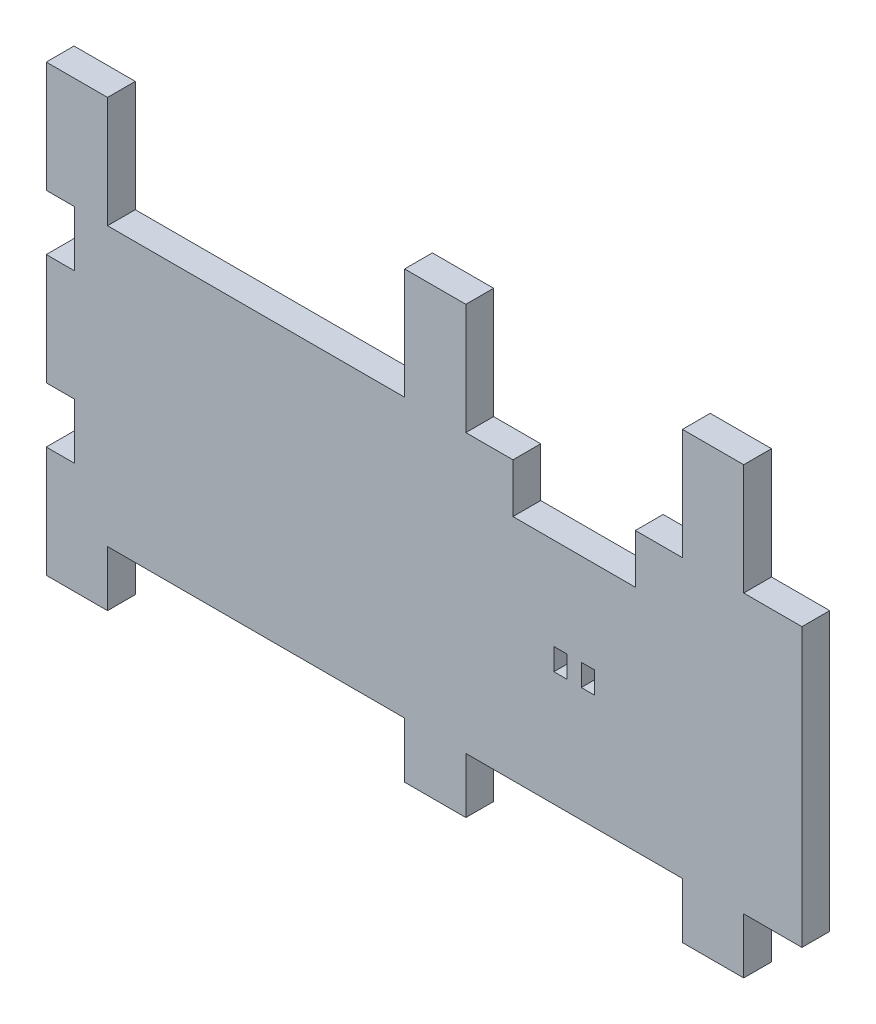
SolidWorks part; units mm, degrees
ref_plane "Front Plane" through (0, 0, 0) normal (0, 0, 1) x (1, 0, 0)
ref_plane "Top Plane" through (0, 0, 0) normal (0, 1, 0) x (1, 0, 0)
ref_plane "Right Plane" through (0, 0, 0) normal (1, 0, 0) x (0, 0, -1)
sketch "Sketch2" plane through (0, 0, 0) normal (0, 0, 1) x (1, 0, 0)
  line L1 (-88.9, -50.8) -> (88.9, -50.8)
  line L2 (-88.9, -50.8) -> (-88.9, 50.8)
  line L3 (-88.9, 50.8) -> (88.9, 50.8)
  line L4 (88.9, -50.8) -> (88.9, 50.8)
  line L5 (-88.9, -50.8) -> (88.9, 50.8) construction
  line L6 (-88.9, 50.8) -> (88.9, -50.8) construction
  point P0 (0, 0)
  dimension "D1" = 101.6
  dimension "D2" = 177.8
extrude "Boss-Extrude3" add sketch "Sketch2" along normal blind 6.35
sketch "Sketch3" plane through (0, 0, 6.35) normal (0, 0, 1) x (1, 0, 0)
  line L0 (-88.9, 50.8) -> (-82.55, 50.8)
  line L1 (-88.9, 50.8) -> (-88.9, 35.56)
  line L2 (-88.9, -50.8) -> (88.9, -50.8) construction
  line L3 (-88.9, 50.8) -> (-74.9, 50.8)
  line L4 (88.9, 50.8) -> (-88.9, 50.8) construction
  line L5 (-82.55, 50.8) -> (-76.2, 50.8)
  line L6 (-14.65, 50.8) -> (-0.65, 50.8)
  line L7 (-88.9, 50.8) -> (-88.9, 35.56)
  line L8 (-7, 50.8) -> (5.3812, 50.8)
  line L9 (-82.4404, 0) -> (-82.4404, 12.7)
  line L10 (-88.9, 50.8) -> (-88.9, -50.8) construction
  line L11 (-7, 50.8) -> (-7, 25.4002)
  line L12 (-88.9, 50.8) -> (-88.9, 25.4002) construction
  line L13 (-82.4404, 25.4002) -> (-82.4404, 12.7)
  line L14 (-82.4404, 25.4002) -> (-74.9, 25.4002)
  line L15 (56.509, 25.4002) -> (56.509, 50.8)
  line L16 (56.509, 25.4002) -> (70.509, 25.4002)
  line L17 (56.509, 50.8) -> (70.509, 50.8)
  line L18 (70.509, 25.4002) -> (70.509, 50.8)
  line L19 (70.509, 25.4002) -> (88.9, 25.4002) construction
  line L20 (-82.55, 50.8) -> (-14.65, 50.8) construction
  line L21 (-0.65, 50.8) -> (56.509, 50.8) construction
  line L22 (70.509, 50.8) -> (88.9, 50.8) construction
  line L23 (70.509, -50.8) -> (88.9, -50.8) construction
  line L24 (-74.9, 50.8) -> (-74.9, 25.4002)
  line L25 (-88.9, -38.1) -> (-74.9, -38.1)
  line L26 (-82.55, 50.8) -> (-14.65, 50.8)
  line L27 (-88.9, -38.1) -> (-88.9, -50.8)
  line L28 (-88.9, -50.8) -> (-74.9, -50.8)
  line L29 (-74.9, -38.1) -> (-74.9, -50.8)
  line L30 (-7, -50.8) -> (-7, -38.1)
  line L31 (70.509, 50.8) -> (70.509, 25.4002)
  line L32 (70.509, 25.4002) -> (88.9, 25.4002)
  line L33 (70.509, 25.4002) -> (70.509, 50.8)
  line L34 (70.509, 50.8) -> (88.9, 50.8)
  line L35 (88.9, 25.4002) -> (88.9, 50.8)
  line L36 (7, -50.8) -> (7, -38.1)
  line L37 (0, -50.8) -> (-0.65, 50.8) construction
  line L38 (70.509, -38.1) -> (88.9, -38.1) construction
  line L39 (-7, -38.1) -> (7, -38.1)
  line L40 (-7, -50.8) -> (-7, -38.1)
  line L41 (88.9, -38.1) -> (88.9, -50.8)
  line L42 (70.509, -50.8) -> (88.9, -50.8)
  line L43 (70.509, -38.1) -> (70.509, -50.8)
  line L44 (70.509, -38.1) -> (88.9, -38.1)
  line L45 (70.509, -50.8) -> (70.509, -38.1)
  line L46 (-7, -50.8) -> (7, -50.8)
  line L47 (-88.9, -44.45) -> (-88.9, -25.4) construction
  line L48 (-7, 50.8) -> (7, 50.8)
  line L49 (-7, 50.8) -> (-7, 25.4002)
  line L50 (-7, 25.4002) -> (7, 25.4002)
  line L51 (7, 50.8) -> (7, 25.4002)
  line L52 (-7, -38.1) -> (7, -38.1)
  line L53 (70.509, -38.1) -> (70.509, -50.8)
  line L54 (56.509, -50.8) -> (70.509, -50.8)
  line L55 (56.509, -38.1) -> (70.509, -38.1)
  line L56 (56.509, -38.1) -> (56.509, -50.8)
  line L57 (-7, -38.1) -> (-7, -50.8)
  line L58 (-82.4404, 0) -> (-82.4404, -12.7)
  line L59 (7, -38.1) -> (7, -50.8)
  line L60 (-74.9, -38.1) -> (-7, -38.1)
  line L61 (-74.9, -38.1) -> (-74.9, -50.8)
  line L62 (-74.9, -50.8) -> (-7, -50.8)
  line L63 (-88.9, -50.8) -> (-88.9, -38.1)
  line L64 (-88.9, -50.8) -> (-82.55, -50.8)
  line L65 (-7, -38.1) -> (-7, -50.8)
  line L66 (7, -38.1) -> (56.509, -38.1)
  line L67 (-82.4404, 25.4002) -> (-82.55, 50.8)
  line L68 (7, -38.1) -> (7, -50.8)
  line L69 (-88.9, 35.56) -> (-88.9, -38.1)
  line L70 (7, -50.8) -> (56.509, -50.8)
  line L71 (-88.9, 0) -> (88.9, 0) construction
  line L72 (-88.9, 38.1) -> (-88.9, 25.4002)
  line L76 (-88.9, 25.4002) -> (-82.4404, 25.4002)
  line L78 (56.509, -38.1) -> (56.509, -50.8)
  line L80 (-88.9, 35.56) -> (-88.9, 25.4002)
  line L81 (-88.9, 25.4002) -> (-82.4404, 25.4002)
  line L83 (-88.9, -38.1) -> (-88.9, -25.4)
  line L84 (-88.9, -25.4) -> (-82.4404, -25.4)
  line L85 (-82.4404, -38.1) -> (-82.4404, -25.4)
  line L86 (-82.55, 50.8) -> (-76.2, 50.8)
  line L87 (56.509, 25.4002) -> (7, 25.4002)
  line L88 (56.509, 25.4002) -> (56.509, 50.8)
  line L90 (-88.9, 12.7) -> (-82.4404, 12.7) construction
  line L91 (-85.725, -12.7) -> (-82.4404, -12.7) construction
  line L92 (-82.4404, -12.7) -> (-88.9, -12.7) construction
  line L93 (-82.55, 50.8) -> (-76.2, 50.8)
  line L94 (-0.65, 50.8) -> (7, 50.8)
  line L95 (56.509, 50.8) -> (7, 50.8)
  line L96 (7, 25.4002) -> (7, 50.8)
  line L97 (7, 50.8) -> (7, 25.4002)
  line L98 (-88.9, -34.925) -> (-82.4404, -34.925) construction
  line L99 (-14.65, 50.8) -> (-7, 50.8)
  line L100 (-74.9, 50.8) -> (-7, 50.8)
  line L102 (-82.4404, 0) -> (-88.9, 0)
  line L103 (-88.9, -34.925) -> (-88.9, 0)
  line L104 (-74.9, 50.8) -> (-74.9, 25.4002)
  line L106 (-82.4404, 12.7) -> (-88.9, 12.7)
  line L107 (-88.9, 38.1) -> (-88.9, 12.7)
  line L108 (-82.4404, -12.7) -> (-88.9, -12.7)
  line L109 (-82.4404, -12.7) -> (-82.4404, -25.4)
  line L110 (-82.4404, -25.4) -> (-88.9, -25.4)
  line L111 (-88.9, -12.7) -> (-88.9, -25.4)
  line L112 (-7, 50.8) -> (-7, 25.4002)
  line L113 (-74.9, 25.4002) -> (-7, 25.4002)
  line L114 (-7, 50.8) -> (-7, 25.4002)
  line L124 (-82.55, -50.8) -> (-76.2, -50.8)
  line L126 (-82.55, -50.8) -> (-76.2, -50.8)
  line L127 (-82.4404, -38.1) -> (-82.4404, -25.4)
  line L140 (-82.55, -50.8) -> (-76.2, -50.8)
  line L143 (-88.9, -50.8) -> (-82.55, -50.8)
  line M62 (88.9, -50.8) -> (88.9, 50.8)
  line M63 (88.9, 50.8) -> (-88.9, 50.8)
  line M64 (-88.9, 50.8) -> (-88.9, -50.8)
  line M65 (-88.9, -50.8) -> (88.9, -50.8)
extrude "Cut-Extrude3" cut sketch "Sketch3" against normal through all contours L106 L76 M64 | L108 L103 L84 | L24 L113 L11 L6 M63 | L87 L15 L51 M63 | L18 L32 M62 M63 | L44 L43 M65 M62 | L66 L36 L56 M65 | L60 L29 L30 M65 region at (-85.6702, 19.0501, 6.35) region at (-40.95, 38.1001, 6.35) region at (-85.6702, -19.05, 6.35) region at (31.7545, 38.1001, 6.35) region at (79.7045, 38.1001, 6.35) region at (-40.95, -44.45, 6.35) region at (79.7045, -44.45, 6.35) region at (31.7545, -44.45, 6.35)
sketch "Sketch4" plane through (0, 0, 0) normal (0, 0, -1) x (-1, 0, 0)
  line L0 (-17.768, 25.4002) -> (-17.768, 14.1602)
  line L1 (-56.509, 25.4002) -> (-7, 25.4002) construction
  line L2 (-17.768, 14.1602) -> (-45.741, 14.1602)
  line L3 (-45.741, 14.1602) -> (-45.741, 25.4002)
  line L4 (-45.741, 25.4002) -> (-17.768, 25.4002)
  line L5 (-88.9, 25.4002) -> (-83.82, 25.4002)
  line L6 (-70.509, 25.4002) -> (-88.9, 25.4002) construction
  line L7 (-83.82, 25.4002) -> (-83.82, -38.1)
  line L8 (-70.509, -38.1) -> (-88.9, -38.1) construction
  line L9 (-83.82, -38.1) -> (-88.9, -38.1)
  line L10 (-88.9, -38.1) -> (-88.9, 25.4002)
  dimension "D1" = 10.768
  dimension "D2" = 10.768
  dimension "D3" = 11.24
  dimension "D4" = 5.08
extrude "Cut-Extrude4" cut sketch "Sketch4" against normal through all
sketch "Sketch5" plane through (0, 0, 0) normal (0, 0, -1) x (-1, 0, 0)
  line L0 (-17.768, 14.1602) -> (-17.768, -38.1158) construction
  line L2 (-27.1291, -11.8658) -> (-27.1291, -6.8658)
  line L3 (-27.1291, -11.8658) -> (-30.1291, -11.8658)
  line L4 (-30.1291, -11.8658) -> (-30.1291, -6.8658)
  line L5 (-27.1291, -6.8658) -> (-30.1291, -6.8658)
  line L6 (-30.1291, -11.8658) -> (-33.3791, -11.8658) construction
  line L7 (-33.3791, -11.8658) -> (-33.3791, -6.8658)
  line L8 (-33.3791, -6.8658) -> (-36.3791, -6.8658)
  line L9 (-36.3791, -6.8658) -> (-36.3791, -11.8658)
  line L10 (-36.3791, -11.8658) -> (-33.3791, -11.8658)
  line L11 (-31.7541, 14.1602) -> (-31.7541, -11.8658) construction
  line L13 (-31.7541, -11.8658) -> (-31.7541, -3.6391) construction
  line L14 (-27.1291, -11.8658) -> (-17.768, -11.9778) construction
  dimension "D1" = 9.3611
  dimension "D2" = 52.276
  dimension "D3" = 5
  dimension "D4" = 3
extrude "Cut-Extrude5" cut sketch "Sketch5" against normal blind 10
